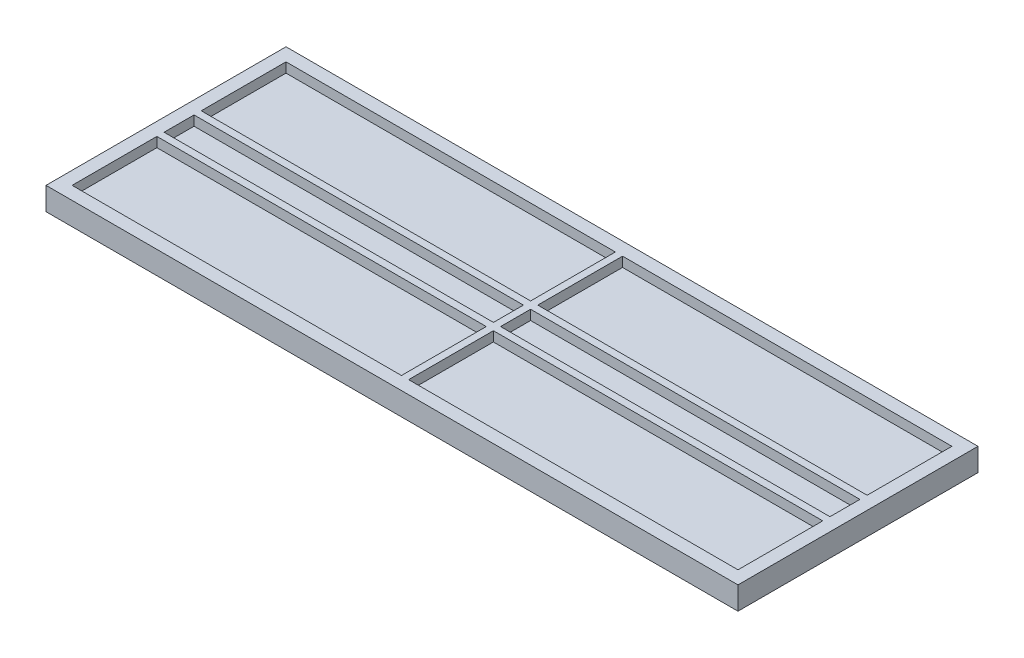
SolidWorks part; units mm, degrees
ref_plane "Front" through (0, 0, 0) normal (0, 0, 1) x (1, 0, 0)
ref_plane "Top" through (0, 0, 0) normal (0, 1, 0) x (1, 0, 0)
ref_plane "Right" through (0, 0, 0) normal (1, 0, 0) x (0, 0, -1)
sketch "Sketch1" plane through (0, 0, 0) normal (0, 1, 0) x (1, 0, 0)
  line L1 (-84.2169, -29.21) -> (84.2169, -29.21)
  line L2 (-84.2169, -29.21) -> (-84.2169, 29.21)
  line L3 (-84.2169, 29.21) -> (84.2169, 29.21)
  line L4 (84.2169, -29.21) -> (84.2169, 29.21)
  line L5 (-84.2169, -29.21) -> (84.2169, 29.21) construction
  line L6 (-84.2169, 29.21) -> (84.2169, -29.21) construction
  point P0 (0, 0)
  dimension "D1" = 168.4338
  dimension "D2" = 58.42
extrude "Boss-Extrude1" add sketch "Sketch1" along normal blind 5.5562
sketch "Sketch2" plane through (0, 5.5562, 0) normal (0, 1, 0) x (1, 0, 0)
  line L0 (-81.0419, -26.035) -> (-81.0419, -29.21) construction
  line L1 (-81.0419, 5.3975) -> (-0.8731, 5.3975)
  line L2 (-81.0419, 5.3975) -> (-81.0419, 26.035)
  line L3 (-81.0419, 26.035) -> (-0.8731, 26.035)
  line L4 (-0.8731, 5.3975) -> (-0.8731, 26.035)
  line L5 (-81.0419, 5.3975) -> (-0.8731, 26.035) construction
  line L6 (-81.0419, 26.035) -> (-0.8731, 5.3975) construction
  line L7 (-81.0419, -26.035) -> (-0.8731, -26.035)
  line L8 (-81.0419, -26.035) -> (-81.0419, -5.3975)
  line L9 (-81.0419, -5.3975) -> (-0.8731, -5.3975)
  line L10 (-0.8731, -26.035) -> (-0.8731, -5.3975)
  line L11 (-81.0419, -26.035) -> (-0.8731, -5.3975) construction
  line L12 (-81.0419, -5.3975) -> (-0.8731, -26.035) construction
  line L13 (0.8731, 5.3975) -> (81.0419, 5.3975)
  line L14 (0.8731, 5.3975) -> (0.8731, 26.035)
  line L15 (0.8731, 26.035) -> (81.0419, 26.035)
  line L16 (81.0419, 5.3975) -> (81.0419, 26.035)
  line L17 (0.8731, 5.3975) -> (81.0419, 26.035) construction
  line L18 (0.8731, 26.035) -> (81.0419, 5.3975) construction
  line L19 (0.8731, -26.035) -> (81.0419, -26.035)
  line L20 (0.8731, -26.035) -> (0.8731, -5.3975)
  line L21 (0.8731, -5.3975) -> (81.0419, -5.3975)
  line L22 (81.0419, -26.035) -> (81.0419, -5.3975)
  line L23 (0.8731, -26.035) -> (81.0419, -5.3975) construction
  line L24 (0.8731, -5.3975) -> (81.0419, -26.035) construction
  line L25 (-84.2169, -29.21) -> (84.2169, -29.21) construction
  line L26 (-81.0419, -26.035) -> (-84.2169, -26.035) construction
  line L27 (-84.2169, 29.21) -> (-84.2169, -29.21) construction
  line L28 (-81.0419, 26.035) -> (-84.2169, 26.035) construction
  line L29 (-81.0419, 26.035) -> (-81.0419, 29.21) construction
  line L30 (84.2169, 29.21) -> (-84.2169, 29.21) construction
  line L31 (81.0419, -26.035) -> (81.0419, -29.21) construction
  line L32 (81.0419, -26.035) -> (84.2169, -26.035) construction
  line L33 (84.2169, -29.21) -> (84.2169, 29.21) construction
  line L34 (-81.0419, -5.3975) -> (-81.0419, -3.65) construction
  line L35 (-81.0419, 3.65) -> (-0.8731, 3.65)
  line L36 (-81.0419, 3.65) -> (-81.0419, -3.65)
  line L37 (-81.0419, -3.65) -> (-0.8731, -3.65)
  line L38 (-0.8731, 3.65) -> (-0.8731, -3.65)
  line L39 (0.8731, 3.65) -> (81.0419, 3.65)
  line L40 (0.8731, 3.65) -> (0.8731, -3.65)
  line L41 (0.8731, -3.65) -> (81.0419, -3.65)
  line L42 (81.0419, 3.65) -> (81.0419, -3.65)
  line L43 (-81.0419, 3.65) -> (-81.0419, 5.3975) construction
  point P0 (-40.9575, 15.7162)
  point P5 (-40.9575, -15.7162)
  point P10 (40.9575, 15.7163)
  point P15 (40.9575, -15.7162)
  dimension "D1" = 3.175
  dimension "D2" = 20.6375
  dimension "D3" = 80.1688
  dimension "D4" = 7.3
extrude "Cut-Extrude1" cut sketch "Sketch2" against normal blind 2.3813
sketch "Sketch3" plane through (0, 3.175, 0) normal (0, 1, 0) x (1, 0, 0)
  line L0 (-79.4544, -15.7162) -> (-81.0419, -15.7162) construction
  line L1 (-79.4544, 24.4475) -> (-2.4606, 24.4475)
  line L2 (-79.4544, 24.4475) -> (-79.4544, 6.985)
  line L3 (-79.4544, 6.985) -> (-2.4606, 6.985)
  line L4 (-2.4606, 24.4475) -> (-2.4606, 6.985)
  line L5 (-79.4544, -6.985) -> (-2.4606, -6.985)
  line L6 (-79.4544, -15.7162) -> (-79.4544, -17.9387) construction
  line L7 (-73.1837, -24.4475) -> (-2.4606, -24.4475)
  line L8 (-2.4606, -6.985) -> (-2.4606, -24.4475)
  line L9 (2.4606, -6.985) -> (79.4544, -6.985)
  line L10 (2.4606, -6.985) -> (2.4606, -24.4475)
  line L11 (2.4606, -24.4475) -> (79.4544, -24.4475)
  line L12 (79.4544, -6.985) -> (79.4544, -24.4475)
  line L13 (2.4606, 24.4475) -> (79.4544, 24.4475)
  line L14 (2.4606, 24.4475) -> (2.4606, 6.985)
  line L15 (2.4606, 6.985) -> (79.4544, 6.985)
  line L16 (79.4544, 24.4475) -> (79.4544, 6.985)
  line L17 (-81.0419, -5.3975) -> (-81.0419, -26.035) construction
  line L18 (-79.4544, 15.7162) -> (-81.0419, 15.7162) construction
  line L19 (-81.0419, 26.035) -> (-81.0419, 5.3975) construction
  line L20 (79.4544, -15.7162) -> (81.0419, -15.7162) construction
  line L21 (81.0419, -26.035) -> (81.0419, -5.3975) construction
  line L22 (79.4544, 15.7163) -> (81.0419, 15.7162) construction
  line L23 (81.0419, 5.3975) -> (81.0419, 26.035) construction
  line L24 (-2.4606, 15.7163) -> (-0.8731, 15.7162) construction
  line L25 (-0.8731, 5.3975) -> (-0.8731, 26.035) construction
  line L26 (0.8731, 15.7162) -> (2.4606, 15.7163) construction
  line L27 (0.8731, 26.035) -> (0.8731, 5.3975) construction
  line L28 (2.4606, -15.7162) -> (0.8731, -15.7162) construction
  line L29 (0.8731, -5.3975) -> (0.8731, -26.035) construction
  line L30 (-0.8731, -15.7162) -> (-2.4606, -15.7162) construction
  line L31 (-0.8731, -26.035) -> (-0.8731, -5.3975) construction
  line L32 (-40.9575, 2.0625) -> (-40.9575, 3.65) construction
  line L33 (-79.4544, 2.0625) -> (-2.4606, 2.0625)
  line L34 (-79.4544, 2.0625) -> (-79.4544, -2.0625)
  line L35 (-79.4544, -2.0625) -> (-2.4606, -2.0625)
  line L36 (-2.4606, 2.0625) -> (-2.4606, -2.0625)
  line L37 (2.4606, 2.0625) -> (79.4544, 2.0625)
  line L38 (2.4606, 2.0625) -> (2.4606, -2.0625)
  line L39 (2.4606, -2.0625) -> (79.4544, -2.0625)
  line L40 (79.4544, 2.0625) -> (79.4544, -2.0625)
  line L41 (-0.8731, 3.65) -> (-81.0419, 3.65) construction
  line L42 (-40.9575, -2.0625) -> (-40.9575, -3.65) construction
  line L43 (-81.0419, -3.65) -> (-0.8731, -3.65) construction
  line L44 (-84.2169, 29.21) -> (-84.2169, -29.21) construction
  line L45 (-82.7087, -17.9387) -> (-73.1837, -17.9387) construction
  line L46 (-82.7087, -17.9387) -> (-82.7087, -27.4637) construction
  line L47 (-82.7087, -27.4637) -> (-73.1837, -27.4637) construction
  line L48 (-73.1837, -17.9387) -> (-73.1837, -27.4637) construction
  line L49 (-84.2169, -29.21) -> (84.2169, -29.21) construction
  line L50 (-79.4544, -24.4475) -> (-73.1837, -24.4475) construction
  line L51 (-79.4544, -17.9387) -> (-79.4544, -24.4475) construction
  line L52 (-79.4544, -6.985) -> (-79.4544, -15.7162) construction
  line L53 (-79.4544, -6.985) -> (-79.4544, -17.9387)
  line L54 (-79.4544, -17.9387) -> (-73.1837, -17.9387)
  line L55 (-73.1837, -17.9387) -> (-73.1837, -24.4475)
  dimension "D1" = 17.4625
  dimension "D2" = 1.5875
  dimension "D3" = 9.525
  dimension "D4" = 1.5081
  dimension "D5" = 1.7463
